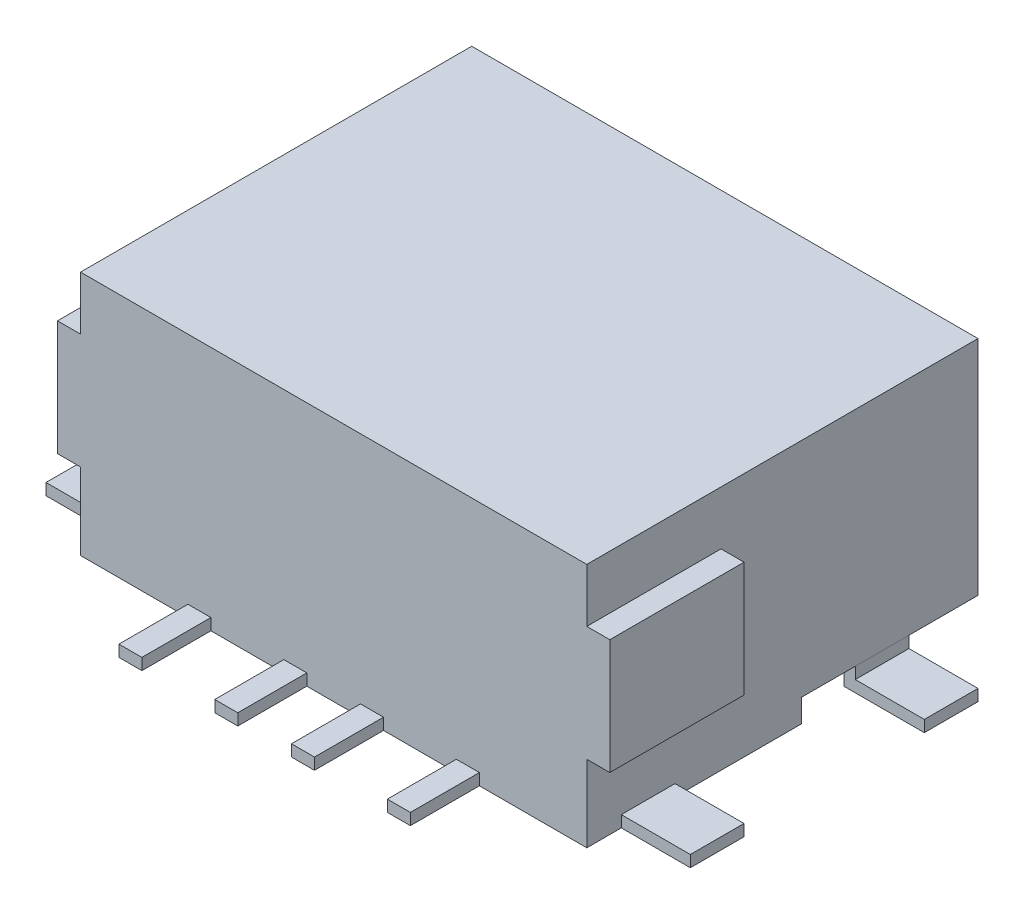
SolidWorks part; units mm, degrees
ref_plane "前视基准面" through (0, 0, 0) normal (0, 0, 1) x (1, 0, 0)
ref_plane "上视基准面" through (0, 0, 0) normal (0, 1, 0) x (1, 0, 0)
ref_plane "右视基准面" through (0, 0, 0) normal (1, 0, 0) x (0, 0, -1)
other "Configuration Table"
sketch "草图1" plane through (0, 0, 0) normal (0, 1, 0) x (1, 0, 0)
  line L22 (-6.6, -5.1) -> (6.6, -5.1)
  line L23 (-6.6, -5.1) -> (-6.6, 5.1)
  line L28 (-6.6, 5.1) -> (6.6, 5.1)
  line L29 (6.6, -5.1) -> (6.6, 5.1)
  line L37 (-6.6, -5.1) -> (6.6, 5.1) construction
  line L38 (-6.6, 5.1) -> (6.6, -5.1) construction
  point P0 (0, 0)
  dimension "D1" = 13.2
  dimension "D2" = 10.2
extrude "凸台-拉伸1" add sketch "草图1" along normal blind 5.8
sketch "草图2" plane through (0, 0, -5.1) normal (0, 0, -1) x (-1, 0, 0)
  line L0 (-6.6, 5.8) -> (-6.6, 0) construction
  line L1 (-6.2, 5.4) -> (6.2, 5.4)
  line L2 (-6.2, 5.4) -> (-6.2, 0.4)
  line L3 (-6.2, 0.4) -> (6.2, 0.4)
  line L4 (6.2, 5.4) -> (6.2, 0.4)
  line L5 (-6.6, 5.8) -> (6.6, 5.8) construction
  line L6 (6.6, 5.8) -> (6.6, 0) construction
  line L7 (-6.6, 0) -> (6.6, 0) construction
  dimension "D1" = 0.4
  dimension "D2" = 0.4
  dimension "D3" = 0.4
  dimension "D4" = 0.4
extrude "切除-拉伸1" cut sketch "草图2" against normal offset from surface (9.8 mm away) 0.4 up to face at (0, 2.9, 5.1)
sketch "草图3" plane through (0, 0, 4.7) normal (0, 0, -1) x (-1, 0, 0)
  line L0 (-6.2, 5.4) -> (-6.2, 0.4) construction
  line L1 (-5.4, 4.4) -> (5.4, 4.4)
  line L2 (-5.4, 4.4) -> (-5.4, 2.9)
  line L3 (-5.4, 2.9) -> (5.4, 2.9)
  line L4 (5.4, 4.4) -> (5.4, 2.9)
  line L5 (6.2, 0.4) -> (6.2, 5.4) construction
  line L6 (-6.2, 5.4) -> (6.2, 5.4) construction
  dimension "D1" = 0.8
  dimension "D2" = 0.8
  dimension "D3" = 1
  dimension "D4" = 1.5
extrude "凸台-拉伸2" add sketch "草图3" along normal up to surface (9.8 mm away) up to face at (0, 2.9, -5.1)
sketch "草图4" plane through (6.6, 0, 0) normal (1, 0, 0) x (0, 0, -1)
  line L0 (-5.1, 5.8) -> (-5.1, 0) construction
  line L1 (-5.1, 4.4) -> (-1.6, 4.4)
  line L2 (-5.1, 4.4) -> (-5.1, 1.4)
  line L3 (-5.1, 1.4) -> (-1.6, 1.4)
  line L4 (-1.6, 4.4) -> (-1.6, 1.4)
  line L5 (-5.1, 5.8) -> (5.1, 5.8) construction
  dimension "D1" = 1.4
  dimension "D2" = 3
  dimension "D3" = 3.5
extrude "凸台-拉伸3" add sketch "草图4" along normal blind 0.6
extrude "凸台-拉伸4" add sketch "草图4<2>" against normal blind 0.6 from surface starting at face at (-6.6, 2.9, 0)
sketch "草图4<2>" plane through (6.6, 0, 0) normal (1, 0, 0) x (0, 0, -1) same geometry as "草图4"
sketch "草图5" plane through (0, 0, 0) normal (0, -1, 0) x (1, 0, 0)
  line L0 (6.6, 5.1) -> (6.6, -5.1) construction
  line L1 (-6.6, 5.1) -> (6.6, 5.1)
  line L2 (-6.6, 5.1) -> (-6.6, -0.5)
  line L3 (-6.6, -0.5) -> (6.6, -0.5)
  line L4 (6.6, 5.1) -> (6.6, -0.5)
  dimension "D1" = 5.6
extrude "凸台-拉伸5" add sketch "草图5" along normal blind 0.6
sketch "草图6" plane through (0, -0.6, 0) normal (0, -1, 0) x (1, 0, 0)
  line L0 (0, 0) -> (0, 5.1) construction
  line L2 (-2.45, 2.7) -> (2.45, 2.7)
  line L3 (6.6, 5.1) -> (-6.6, 5.1) construction
  circle A0 centre (-2.45, 3.45) radius 0.75
  circle A1 centre (2.45, 3.45) radius 0.75
  point P9 (-2.45, 1.6317)
  dimension "D1" = 1.5
  dimension "D2" = 2.45
  dimension "D3" = 2.45
  dimension "D4" = 2.4
extrude "凸台-拉伸6" add sketch "草图6" along normal blind 0.4 contours A0 | A1
sketch "草图7" plane through (0, -0.6, 0) normal (0, -1, 0) x (1, 0, 0)
  line L0 (-6.6, 5.1) -> (-6.6, -0.5) construction
  line L1 (-6.6, 4.2) -> (-8.4, 4.2)
  line L2 (-6.6, 4.2) -> (-6.6, 2.8)
  line L3 (-6.6, 2.8) -> (-8.4, 2.8)
  line L4 (-8.4, 4.2) -> (-8.4, 2.8)
  line L5 (6.6, 5.1) -> (6.6, 1.6) construction
  line L6 (6.6, 4.2) -> (8.4, 4.2)
  line L7 (6.6, 4.2) -> (6.6, 2.8)
  line L8 (6.6, 2.8) -> (8.4, 2.8)
  line L9 (8.4, 4.2) -> (8.4, 2.8)
  line L10 (-6.6, -5.1) -> (-6.6, -0.5) construction
  line L11 (-6.6, -1.9) -> (-8.4, -1.9)
  line L12 (-6.6, -1.9) -> (-6.6, -3.3)
  line L13 (-6.6, -3.3) -> (-8.4, -3.3)
  line L14 (-8.4, -1.9) -> (-8.4, -3.3)
  line L15 (6.6, -0.5) -> (6.6, -5.1) construction
  line L16 (6.6, -1.9) -> (8.4, -1.9)
  line L17 (6.6, -1.9) -> (6.6, -3.3)
  line L18 (6.6, -3.3) -> (8.4, -3.3)
  line L19 (8.4, -1.9) -> (8.4, -3.3)
  line L20 (6.6, 5.1) -> (-6.6, 5.1) construction
  line L21 (6.6, -5.1) -> (-6.6, -5.1) construction
  dimension "D1" = 1.8
  dimension "D2" = 1.4
  dimension "D3" = 2.3
  dimension "D4" = 3.2
extrude "凸台-拉伸7" add sketch "草图7" against normal blind 0.3
sketch "草图8" plane through (6.6, 0, 0) normal (-1, 0, 0) x (0, 0, 1)
  line L0 (-5.1, 0) -> (-0.5, 0) construction
  line L1 (-3.3, -0.6) -> (-1.9, -0.6)
  line L2 (-3.3, -0.6) -> (-3.3, 0)
  line L3 (-3.3, 0) -> (-1.9, 0)
  line L4 (-1.9, -0.6) -> (-1.9, 0)
  line L5 (-1.9, -0.3) -> (-1.9, -0.6) construction
  point P7 (0, 0)
extrude "凸台-拉伸9" add sketch "草图8" along normal blind 0.3
extrude "凸台-拉伸10" add sketch "草图8<2>" against normal blind 0.3 from surface starting at face at (-6.6, -0.45, -2.6)
sketch "草图8<2>" plane through (6.6, 0, 0) normal (-1, 0, 0) x (0, 0, 1) same geometry as "草图8"
sketch "草图9" plane through (0, 0, 5.1) normal (0, 0, 1) x (1, 0, 0)
  line L0 (6.6, -0.6) -> (-6.6, -0.6) construction
  line L1 (-3.8, -0.3) -> (-3.2, -0.3)
  line L2 (-3.8, -0.3) -> (-3.8, -0.6)
  line L3 (-3.8, -0.6) -> (-3.2, -0.6)
  line L4 (-3.2, -0.3) -> (-3.2, -0.6)
  line L5 (-3.5, -0.3) -> (-3.5, -0.6)
  line L6 (-1.3, -0.3) -> (-0.7, -0.3)
  line L7 (-1.3, -0.3) -> (-1.3, -0.6)
  line L8 (-1.3, -0.6) -> (-0.7, -0.6)
  line L9 (-0.7, -0.3) -> (-0.7, -0.6)
  line L10 (1.3, -0.3) -> (0.7, -0.3)
  line L11 (1.3, -0.3) -> (1.3, -0.6)
  line L12 (1.3, -0.6) -> (0.7, -0.6)
  line L13 (0.7, -0.3) -> (0.7, -0.6)
  line L14 (3.8, -0.3) -> (3.2, -0.3)
  line L15 (3.8, -0.3) -> (3.8, -0.6)
  line L16 (3.8, -0.6) -> (3.2, -0.6)
  line L17 (3.2, -0.3) -> (3.2, -0.6)
  line L18 (-1, -0.3) -> (-1, -0.6)
  line L19 (1, -0.3) -> (1, -0.6)
  line L20 (3.5, -0.3) -> (3.5, -0.6)
  dimension "D1" = 7
  dimension "D2" = 2
  dimension "D3" = 1
  dimension "D4" = 0.6
  dimension "D5" = 3.5
  dimension "D6" = 0.3
extrude "凸台-拉伸11" add sketch "草图9" along normal blind 1.8 contours L4 L3 L2 L1 | L7 L8 L9 L6 | L13 L12 L11 L10 | L17 L16 L15 L14
